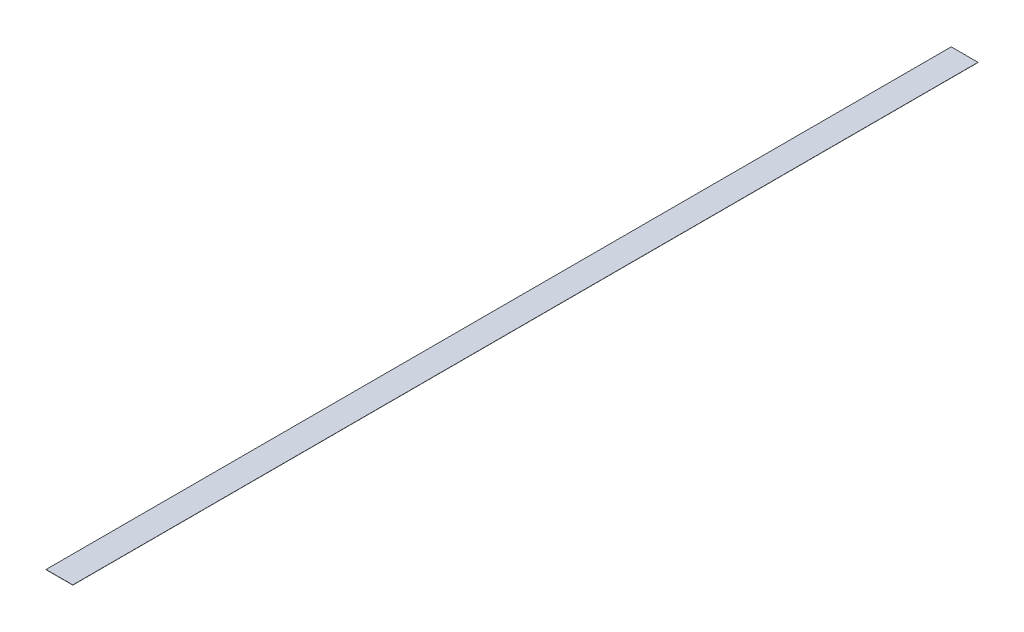
SolidWorks part; units mm, degrees
material "Kapton Film"
ref_plane "Front Plane" through (0, 0, 0) normal (0, 0, 1) x (1, 0, 0)
ref_plane "Top Plane" through (0, 0, 0) normal (0, 1, 0) x (1, 0, 0)
ref_plane "Right Plane" through (0, 0, 0) normal (1, 0, 0) x (0, 0, -1)
sketch "Sketch1" plane through (0, 0, 0) normal (0, 1, 0) x (1, 0, 0)
  line L5 (0, 0) -> (15, 0)
  line L6 (0, 0) -> (0, -507)
  line L7 (0, -507) -> (15, -507)
  line L8 (15, 0) -> (15, -507)
  dimension "D1" = 507
  dimension "D2" = 15
extrude "Boss-Extrude1" add sketch "Sketch1" along normal blind 0.1 contours L6 L7 L8 L5
sketch "Sketch2" plane through (0, 0.1, 0) normal (0, 1, 0) x (1, 0, 0)
  line L0 (0, -487) -> (15, -483.537) construction
  line L1 (0, 0) -> (0, -507) construction
  line L2 (15, 0) -> (15, -507) construction
  line L3 (5.0641, -485.8309) -> (5.0641, -457.2309) construction
  circle A0 centre (5.0641, -485.8309) radius 1
  circle A1 centre (9.9359, -484.7061) radius 1
  circle A2 centre (5.0641, -457.2309) radius 1
  circle A3 centre (9.9359, -456.1061) radius 1
  circle A4 centre (5.0641, -428.6309) radius 1
  circle A5 centre (9.9359, -427.5061) radius 1
  circle A6 centre (5.0641, -400.0309) radius 1
  circle A7 centre (9.9359, -398.9061) radius 1
  circle A8 centre (5.0641, -371.4309) radius 1
  circle A9 centre (9.9359, -370.3061) radius 1
  circle A10 centre (5.0641, -342.8309) radius 1
  circle A11 centre (9.9359, -341.7061) radius 1
  circle A12 centre (5.0641, -314.2309) radius 1
  circle A13 centre (9.9359, -313.1061) radius 1
  circle A14 centre (5.0641, -285.6309) radius 1
  circle A15 centre (9.9359, -284.5061) radius 1
  circle A16 centre (5.0641, -257.0309) radius 1
  circle A17 centre (9.9359, -255.9061) radius 1
  circle A18 centre (5.0641, -228.4309) radius 1
  circle A19 centre (9.9359, -227.3061) radius 1
  circle A20 centre (5.0641, -199.8309) radius 1
  circle A21 centre (9.9359, -198.7061) radius 1
  circle A22 centre (5.0641, -171.2309) radius 1
  circle A23 centre (9.9359, -170.1061) radius 1
  circle A24 centre (5.0641, -142.6309) radius 1
  circle A25 centre (9.9359, -141.5061) radius 1
  circle A26 centre (5.0641, -114.0309) radius 1
  circle A27 centre (9.9359, -112.9061) radius 1
  circle A28 centre (5.0641, -85.4309) radius 1
  circle A29 centre (9.9359, -84.3061) radius 1
  circle A30 centre (5.0641, -56.8309) radius 1
  circle A31 centre (9.9359, -55.7061) radius 1
  point P13 (7.5, -485.2685)
  dimension "D3" = 2
  dimension "D4" = 5
  dimension "D1" = 20
  dimension "D2" = 77
  dimension "D5" = 2.5
  dimension "D7" = 28.6
  dimension "D6" = 16
extrude "Cut-Extrude1" [suppressed] cut sketch "Sketch2" against normal through all
ref_plane "Plane1" through (7.5, 0, 0) normal (1, 0, 0) x (0, 0, -1)
sketch "Sketch3" [suppressed] plane through (0, 0.1, 0) normal (0, 1, 0) x (1, 0, 0)
  line L5 (15, 0) -> (15, -507) construction
  line L6 (0, 0) -> (15, 0)
  line L7 (0, 0) -> (0, -492)
  line L8 (0, -492) -> (15, -492)
  line L9 (15, 0) -> (15, -492)
  dimension "D1" = 15
extrude "Cut-Extrude2" [suppressed] cut sketch "Sketch3" against normal blind 10
